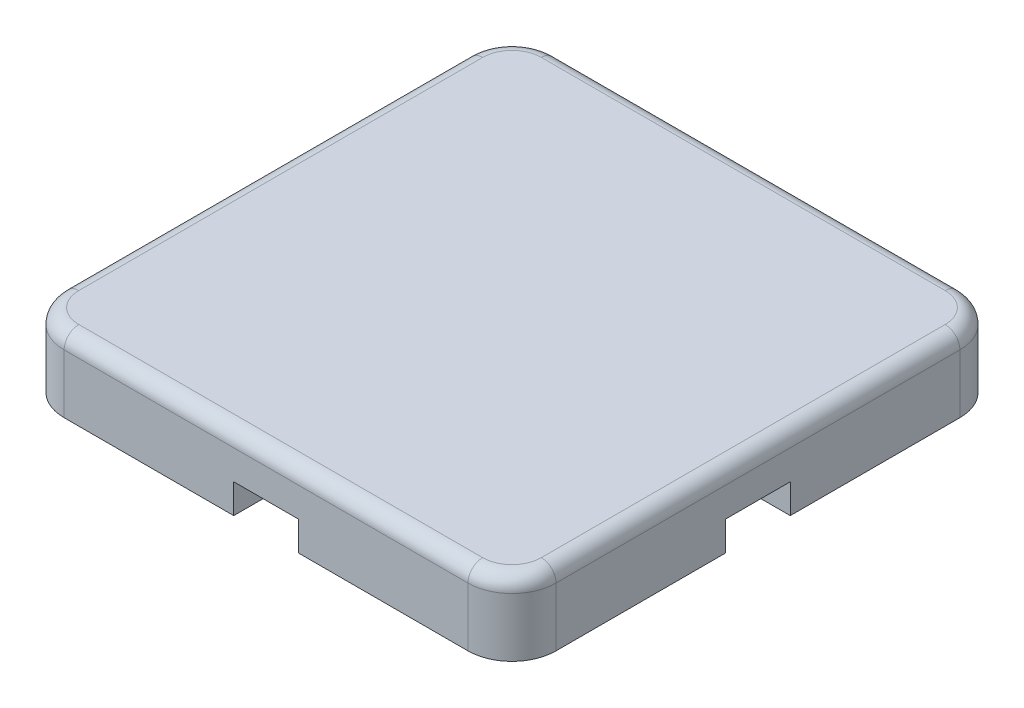
SolidWorks part; units mm, degrees
material "TPU 98A"
ref_plane "Front Plane" through (0, 0, 0) normal (0, 0, 1) x (1, 0, 0)
ref_plane "Top Plane" through (0, 0, 0) normal (0, 1, 0) x (1, 0, 0)
ref_plane "Right Plane" through (0, 0, 0) normal (1, 0, 0) x (0, 0, -1)
sketch "Sketch1" plane through (0, 0, 0) normal (0, 1, 0) x (1, 0, 0)
  line L1 (-13.75, -16.75) -> (13.75, -16.75)
  line L2 (-16.75, -13.75) -> (-16.75, 13.75)
  line L3 (-13.75, 16.75) -> (13.75, 16.75)
  line L4 (16.75, -13.75) -> (16.75, 13.75)
  line L5 (-16.75, -16.75) -> (16.75, 16.75) construction
  line L6 (-16.75, 16.75) -> (16.75, -16.75) construction
  arc A0 (-13.75, -16.75) -> (-16.75, -13.75) centre (-13.75, -13.75) cw
  arc A1 (13.75, -16.75) -> (16.75, -13.75) centre (13.75, -13.75) ccw
  arc A2 (13.75, 16.75) -> (16.75, 13.75) centre (13.75, 13.75) cw
  arc A3 (-16.75, 13.75) -> (-13.75, 16.75) centre (-13.75, 13.75) cw
  point P0 (0, 0)
  dimension "D2" = 3
  dimension "D1" = 33.5
extrude "Boss-Extrude1" add sketch "Sketch1" along normal blind 5
shell "Shell1" thickness 2 removed face at (0, 0, 0)
fillet "Fillet1" radius 1 8 edges at (-16.75, 5, 0) (-15.8713, 5, -15.8713) (0, 5, -16.75) (15.8713, 5, -15.8713) (16.75, 5, 0) (15.8713, 5, 15.8713) (0, 5, 16.75) (-15.8713, 5, 15.8713)
sketch "Sketch2" plane through (0, 3, 0) normal (0, -1, 0) x (1, 0, 0)
  circle A0 centre (0, 0) radius 8.5
  dimension "D1" = 17
extrude "Boss-Extrude2" add sketch "Sketch2" along normal blind 1.6
sketch "Sketch3" plane through (0, 0, 0) normal (0, -1, 0) x (1, 0, 0)
  line L0 (0, 16.75) -> (0, -16.75) construction
  line L1 (-13.75, 16.75) -> (13.75, 16.75) construction
  line L2 (13.75, -16.75) -> (-13.75, -16.75) construction
  line L3 (-16.75, 0) -> (16.75, 0) construction
  line L4 (-16.75, -13.75) -> (-16.75, 13.75) construction
  line L5 (16.75, 13.75) -> (16.75, -13.75) construction
  line L6 (-2.2, 16.75) -> (-2.2, 14.75)
  line L7 (-16.75, -2.2) -> (-14.75, -2.2)
  line L8 (2.2, 16.75) -> (2.2, 14.75)
  line L9 (-16.75, 2.2) -> (-14.75, 2.2)
  line L10 (13.75, -14.75) -> (-13.75, -14.75) construction
  line L11 (-14.75, -13.75) -> (-14.75, 13.75) construction
  line L12 (-13.75, 14.75) -> (13.75, 14.75) construction
  line L13 (14.75, 13.75) -> (14.75, -13.75) construction
  line L14 (2.2, -14.75) -> (-2.2, -14.75)
  line L15 (-14.75, -2.2) -> (-14.75, 2.2)
  line L16 (-2.2, 14.75) -> (2.2, 14.75)
  line L17 (14.75, 2.2) -> (14.75, -2.2)
  line L18 (14.75, 2.2) -> (16.75, 2.2)
  line L19 (2.2, 16.75) -> (2.2, -16.75) construction
  line L20 (2.2, -16.75) -> (-2.2, -16.75)
  line L21 (-2.2, 16.75) -> (-2.2, -16.75) construction
  line L22 (2.2, -14.75) -> (2.2, -16.75)
  line L23 (-2.2, -14.75) -> (-2.2, -16.75)
  line L24 (-16.75, 2.2) -> (16.75, 2.2) construction
  line L25 (14.75, -2.2) -> (16.75, -2.2)
  line L26 (-16.75, -2.2) -> (16.75, -2.2) construction
  line L27 (-16.75, -2.2) -> (-16.75, 2.2)
  line L28 (-2.2, 16.75) -> (2.2, 16.75)
  line L29 (16.75, 2.2) -> (16.75, -2.2)
  dimension "D1" = 2.2
  dimension "D2" = 2.2
extrude "Cut-Extrude1" cut sketch "Sketch3" against normal blind 2
equation "\"D1@Sketch3\"=\"D2@Sketch3\""
